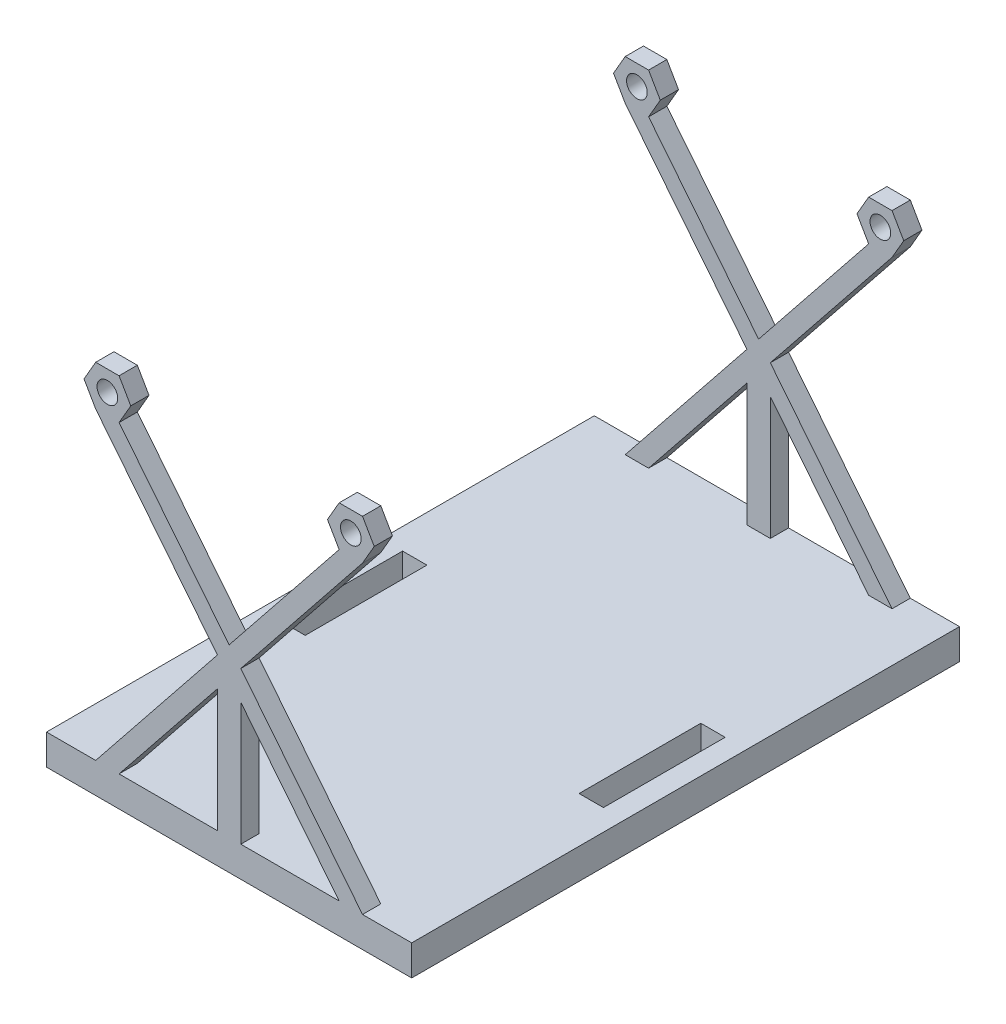
SolidWorks part; units mm, degrees
ref_plane "Front Plane" through (0, 0, 0) normal (0, 0, 1) x (1, 0, 0)
ref_plane "Top Plane" through (0, 0, 0) normal (0, 1, 0) x (1, 0, 0)
ref_plane "Right Plane" through (0, 0, 0) normal (1, 0, 0) x (0, 0, -1)
sketch "Sketch2" plane through (0, 0, 0) normal (0, 1, 0) x (1, 0, 0)
  line L0 (-30, 0) -> (-19, 0) construction
  line L1 (-30, -45) -> (30, -45)
  line L2 (-30, -45) -> (-30, 45)
  line L3 (-30, 45) -> (30, 45)
  line L4 (30, -45) -> (30, 45)
  line L5 (-30, -45) -> (30, 45) construction
  line L6 (-30, 45) -> (30, -45) construction
  line L7 (-19, -39.5) -> (19, -39.5) construction
  line L8 (-19, -39.5) -> (-19, 39.5) construction
  line L9 (-19, 39.5) -> (19, 39.5) construction
  line L10 (19, -39.5) -> (19, 39.5) construction
  line L11 (-19, -39.5) -> (19, 39.5) construction
  line L12 (-19, 39.5) -> (19, -39.5) construction
  line L13 (-26.5, 10) -> (-22.5, 10)
  line L14 (-26.5, 10) -> (-26.5, -10)
  line L15 (-26.5, -10) -> (-22.5, -10)
  line L16 (-22.5, 10) -> (-22.5, -10)
  line L17 (0, -49.5) -> (0, 49.5) construction
  line L18 (26.5, -10) -> (22.5, -10)
  line L19 (22.5, 10) -> (22.5, -10)
  line L20 (26.5, 10) -> (22.5, 10)
  line L21 (26.5, 10) -> (26.5, -10)
  point P0 (0, 0)
  point P6 (0, 0)
  point P15 (-19, 0)
  point P16 (-22.5, 0)
  point P19 (-24.5, 0)
  point P20 (-24.5, 10)
  dimension "D1" = 60
  dimension "D2" = 90
  dimension "D3" = 79
  dimension "D4" = 38
  dimension "D5" = 20
  dimension "D6" = 4
extrude "Boss-Extrude1" add sketch "Sketch2" along normal mid plane 5
sketch "Sketch3" plane through (0, 0, 45) normal (0, 0, 1) x (1, 0, 0)
  line L0 (-30, 2.5) -> (30, 2.5) construction
  line L1 (-30, 2.5) -> (30, 2.5) construction
  line L2 (-20, 2.5) -> (20, 52.5) construction
  line L3 (-21.9209, 2.5) -> (18.0791, 52.5)
  line L4 (21.9209, 52.5) -> (-18.0791, 2.5)
  line L5 (21.9209, 52.5) -> (18.0791, 52.5)
  line L6 (-18.0791, 2.5) -> (-21.9209, 2.5)
  line L7 (0, -2.75) -> (0, 2.75) construction
  line L8 (-21.9209, 52.5) -> (18.0791, 2.5)
  line L9 (-21.9209, 52.5) -> (-18.0791, 52.5)
  line L10 (21.9209, 2.5) -> (-18.0791, 52.5)
  line L11 (18.0791, 2.5) -> (21.9209, 2.5)
  line L13 (-1.9209, 2.5) -> (1.9209, 2.5)
  line L14 (-1.9209, 2.5) -> (-1.9209, 52.5)
  line L15 (-1.9209, 52.5) -> (1.9209, 52.5)
  line L16 (1.9209, 2.5) -> (1.9209, 52.5)
  line L17 (-1.9209, 2.5) -> (1.9209, 52.5) construction
  line L18 (-1.9209, 52.5) -> (1.9209, 2.5) construction
  point P4 (0, 2.5)
  point P5 (0, 27.5)
  point P8 (20, 52.5)
  point P17 (0, 27.5)
  point P22 (1.9209, 27.5)
  line M13 (30, 2.5) -> (-30, 2.5)
  dimension "D1" = 50
  dimension "D2" = 20
  dimension "D3" = 1.5
extrude "Boss-Extrude2" add sketch "Sketch3" against normal blind 3 contours L8 L3 L4 M13 | L10 L4 L5 L3 | L3 L10 L9 L8 | L16 L8 L4 L14 M13 | L10 L16 L3 | L14 L4 L8 | L8 L11 L10 L9 region at (-10.9945, 13.8419, 45) region at (-1.2806, 25.0988, 45) region at (-10.9945, 41.1581, 45) region at (1.2806, 29.9012, 45) region at (0, 13.2103, 45) region at (10.9945, 41.1581, 45)
sketch "Sketch6" plane through (0, 0, 45) normal (0, 0, 1) x (1, 0, 0)
  line L0 (21.9209, 52.5) -> (1.9209, 27.5) construction
  line L1 (21.9209, 52.5) -> (1.9209, 27.5) construction
  line L2 (21.9209, 52.5) -> (18.0791, 52.5) construction
  line L3 (21.9209, 52.5) -> (18.0791, 52.5) construction
  line L4 (0, -2.75) -> (0, 2.75) construction
  line L5 (21.9209, 59.1543) -> (18.0791, 59.1543)
  line L6 (18.0791, 59.1543) -> (16.1581, 55.8272)
  line L7 (16.1581, 55.8272) -> (18.0791, 52.5)
  line L8 (18.0791, 52.5) -> (21.9209, 52.5)
  line L9 (21.9209, 52.5) -> (23.8419, 55.8272)
  line L10 (23.8419, 55.8272) -> (21.9209, 59.1543)
  line L11 (-23.8419, 55.8272) -> (-21.9209, 59.1543)
  line L12 (-21.9209, 52.5) -> (-23.8419, 55.8272)
  line L13 (-18.0791, 52.5) -> (-21.9209, 52.5)
  line L14 (-16.1581, 55.8272) -> (-18.0791, 52.5)
  line L15 (-18.0791, 59.1543) -> (-16.1581, 55.8272)
  line L16 (-21.9209, 59.1543) -> (-18.0791, 59.1543)
  circle A1 centre (20, 55.8272) radius 3.3272 construction
  point P5 (32.589, 59.1543)
  point P15 (0, 0)
extrude "Boss-Extrude3" add sketch "Sketch6" against normal blind 3
hole_wizard "M3 Clearance Hole1" positions "Sketch7" profile "Sketch8" hole size "M3" standard "ANSI Metric"
sketch "Sketch7" plane through (0, 0, 45) normal (0, 0, 1) x (1, 0, 0)
  line L0 (21.9209, 59.1543) -> (18.0791, 59.1543) construction
  line L1 (16.1581, 55.8272) -> (18.0791, 52.5) construction
  line L2 (21.9209, 52.5) -> (23.8419, 55.8272) construction
  line L3 (-18.0791, 59.1543) -> (-21.9209, 59.1543) construction
  line L4 (-23.8419, 55.8272) -> (-21.9209, 52.5) construction
  line L5 (-18.0791, 52.5) -> (-16.1581, 55.8272) construction
  circle A0 centre (20, 55.8272) radius 3.3272 construction
  circle A1 centre (-20, 55.8272) radius 3.3272 construction
  point P1 (20, 55.8272)
  point P10 (-20, 55.8272)
sketch "Sketch8" plane through (20, 55.8272, 45) normal (1, 0, 0) x (0, -1, 0)
  line L0 (0, 0) -> (0, 88.0205)
  line L1 (0, 88.0205) -> (1.7, 86.999)
  line L2 (1.7, 86.999) -> (1.7, 0)
  line L5 (1.7, 0) -> (0, 0)
  line L10 (0, 88.0205) -> (-1.7, 86.999) construction
  line L11 (0, -6.35) -> (0, 107.95) construction
  dimension "Hole Dia." = 3.4
  dimension "Hole Depth" = 86.999
  dimension "Drill Angle" = 118
mirror "Mirror1" about plane through (0, 0, 0) normal (0, 0, 1) of "M3 Clearance Hole1", "Boss-Extrude3", "Boss-Extrude2"
